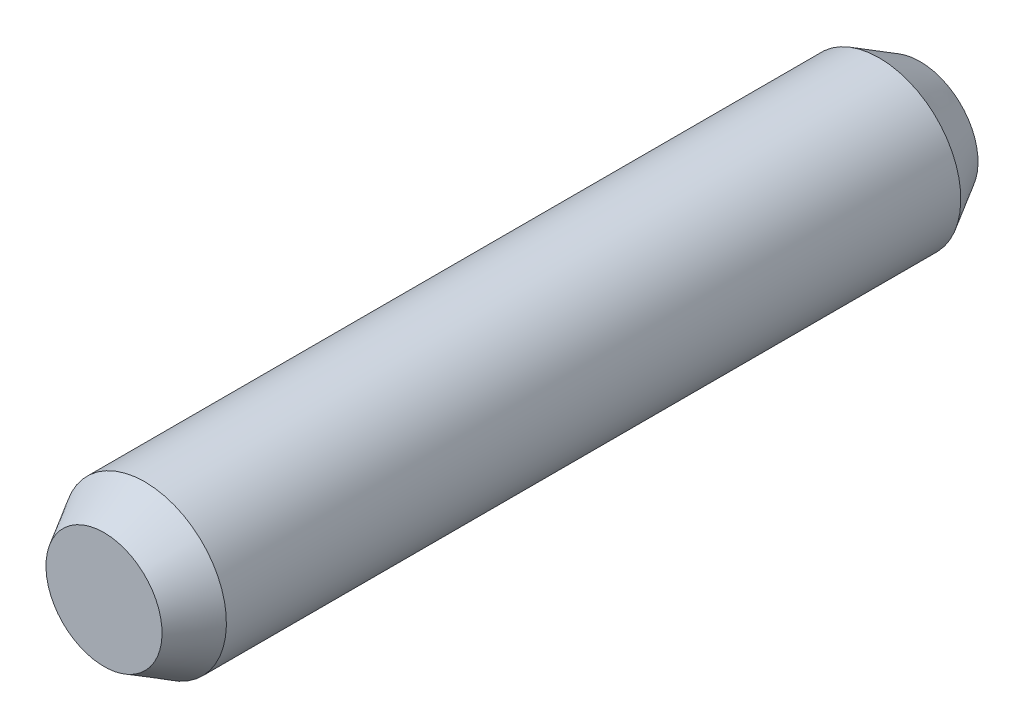
SolidWorks part; units mm, degrees
ref_plane "Ebene vorne" through (0, 0, 0) normal (0, 0, 1) x (1, 0, 0)
ref_plane "Ebene oben" through (0, 0, 0) normal (0, 1, 0) x (1, 0, 0)
ref_plane "Ebene rechts" through (0, 0, 0) normal (1, 0, 0) x (0, 0, -1)
sketch "Skizze1" plane through (0, 0, 0) normal (1, 0, 0) x (0, 0, -1)
  line L0 (-27, 6) -> (27, 6)
  line L1 (27, 6) -> (30, 4.2679)
  line L2 (30, 4.2679) -> (30, 0)
  line L3 (11, 0) -> (-11, 0) construction
  line L4 (30, 0) -> (-30, 0)
  line L5 (-30, 0) -> (-30, 4.2679)
  line L6 (-30, 4.2679) -> (-27, 6)
  line L7 (0, 11) -> (0, -11) construction
  line L8 (0, 50.8437) -> (0, -37.1399) construction
  line L9 (-41.3685, 0) -> (68.2338, 0) construction
  dimension "D1" = 6
  dimension "D2" = 60
  dimension "D5" = 3
  dimension "D3" = 30
revolve "Rotation1" add sketch "Skizze1" angle 360 about L4
sketch "Skizze2" plane through (0, 0, 0) normal (0, 1, 0) x (1, 0, 0)
  line L1 (0, -11) -> (0, 11) construction
  line L2 (-4.2679, -30) -> (4.2679, -30) construction
  line L3 (4.2679, 30) -> (-4.2679, 30) construction
  circle A1 centre (0, -24.5) radius 1.6
  circle A2 centre (0, 24) radius 1.6
  dimension "D1" = 3.2
  dimension "D2" = 5.5
  dimension "D3" = 6
extrude "Schnitt-Linear austragen1" [suppressed] cut sketch "Skizze2" against normal blind 10 and the other way blind 10
equation "\"diameter\"=12.0"
equation "\"length\"=60.0"
equation "\"chamfer_height_30\"=3.0"
equation "\"hole_diameter\"=3.2"
equation "\"hole_distance\"=5.5"
equation "\"D1@Skizze1\"= \"diameter\" / 2"
equation "\"D2@Skizze1\"= \"length\""
equation "\"D5@Skizze1\"= \"chamfer_height_30\""
equation "\"D1@Skizze2\"= \"hole_diameter\""
equation "\"D2@Skizze2\"= \"hole_distance\""
